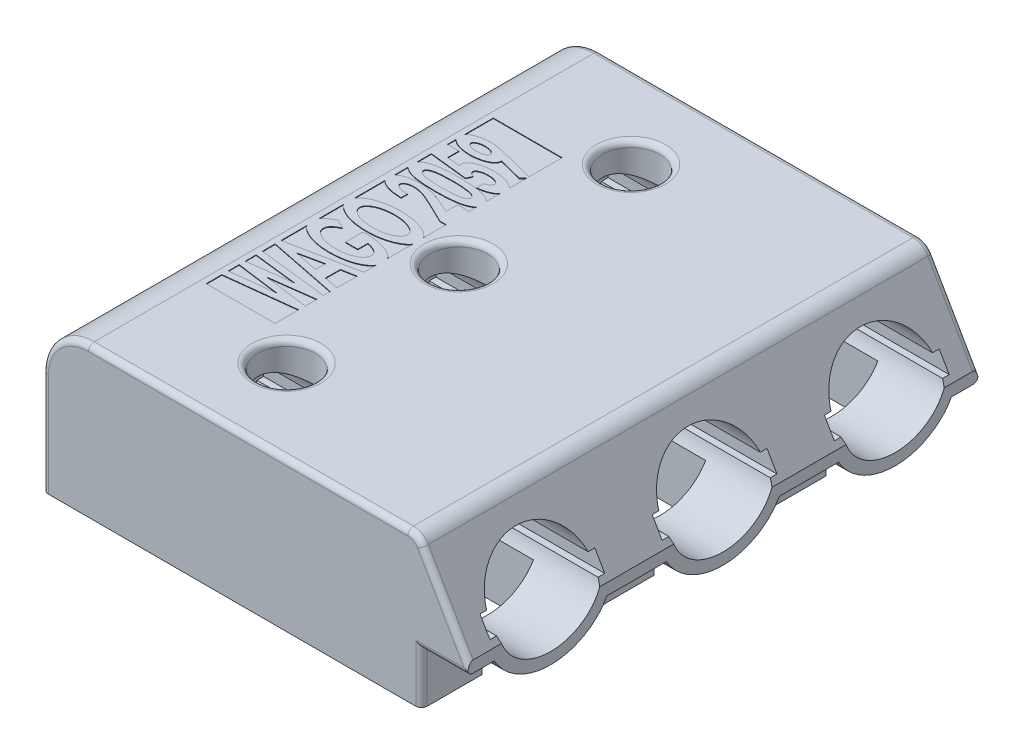
SolidWorks part; units mm, degrees
material "ABS"
ref_plane "Front Plane" through (0, 0, 0) normal (0, 0, 1) x (1, 0, 0)
ref_plane "Top Plane" through (0, 0, 0) normal (0, 1, 0) x (1, 0, 0)
ref_plane "Right Plane" through (0, 0, 0) normal (1, 0, 0) x (0, 0, -1)
sketch "Sketch1" plane through (0, 0, 0) normal (0, 1, 0) x (1, 0, 0)
  line L1 (0, 0) -> (7.4, 0)
  line L2 (0, 0) -> (0, 8.9)
  line L3 (0, 8.9) -> (7.4, 8.9)
  line L4 (7.4, 0) -> (7.4, 8.9)
  dimension "D1" = 8.9
  dimension "D2" = 7.4
extrude "Boss-Extrude1" add sketch "Sketch1" along normal blind 2.6
sketch "Sketch2" plane through (7.4, 0, 0) normal (1, 0, 0) x (0, 0, -1)
  line L0 (0, 2.6) -> (0, 0) construction
  line L1 (0, 0) -> (8.9, 0) construction
  ellipse E0 centre (1.45, 1.35) end of major axis (2.35, 1.35) minor radius 0.8
  ellipse E1 centre (4.45, 1.35) end of major axis (5.35, 1.35) minor radius 0.8
  ellipse E2 centre (7.45, 1.35) end of major axis (8.35, 1.35) minor radius 0.8
  dimension "D1" = 1.45
  dimension "D2" = 1.35
extrude "Cut-Extrude1" cut sketch "Sketch2" against normal blind 6
sketch "Sketch3" plane through (0, 2.6, 0) normal (0, 1, 0) x (1, 0, 0)
  line L0 (0, 8.9) -> (0, 0) construction
  line L1 (0, 0) -> (7.4, 0) construction
  circle A0 centre (2.8, 1.45) radius 0.5
  circle A1 centre (2.8, 4.45) radius 0.5
  circle A2 centre (2.8, 7.45) radius 0.5
  dimension "D1" = 1
  dimension "D3" = 1.45
  dimension "D2" = 2.8
  dimension "D4" = 3
extrude "Cut-Extrude2" cut sketch "Sketch3" against normal up to next
sketch "Sketch4" plane through (7.4, 0, 0) normal (1, 0, 0) x (0, 0, -1)
  line L0 (0, 2.6) -> (0, 0) construction
  line L1 (0.45, 1.5) -> (2.45, 1.5)
  line L2 (0.45, 1.5) -> (0.45, 1.2)
  line L3 (0.45, 1.2) -> (2.45, 1.2)
  line L4 (2.45, 1.5) -> (2.45, 1.2)
  line L6 (0, 0) -> (8.9, 0) construction
  line L7 (8.9, 2.6) -> (8.9, 0) construction
  line L8 (3.45, 1.5) -> (5.45, 1.5)
  line L9 (3.45, 1.5) -> (3.45, 1.2)
  line L10 (3.45, 1.2) -> (5.45, 1.2)
  line L11 (5.45, 1.5) -> (5.45, 1.2)
  line L12 (6.45, 1.5) -> (8.45, 1.5)
  line L13 (6.45, 1.5) -> (6.45, 1.2)
  line L14 (6.45, 1.2) -> (8.45, 1.2)
  line L15 (8.45, 1.5) -> (8.45, 1.2)
  dimension "D1" = 0.3
  dimension "D2" = 2
  dimension "D3" = 0.45
  dimension "D4" = 1.2
  dimension "D5" = 2
  dimension "D6" = 2
  dimension "D7" = 0.3
  dimension "D8" = 0.3
  dimension "D9" = 1.2
  dimension "D10" = 1.2
  dimension "D11" = 0.45
  dimension "D12" = 1
extrude "Cut-Extrude3" cut sketch "Sketch4" against normal blind 6
chamfer "Chamfer2" distance 1.5 angle 30 1 edges at (7.4, 2.6, -4.45) first distance on face at (7.4, 1.35, -7.45)
sketch "Sketch5" plane through (0, 0, 0) normal (0, -1, 0) x (1, 0, 0)
  line L1 (0.8, -8.25) -> (6.3, -8.25)
  line L2 (0.8, -8.25) -> (0.8, -6.65)
  line L3 (0.8, -6.65) -> (6.3, -6.65)
  line L4 (6.3, -8.25) -> (6.3, -6.65)
  line L5 (0, -8.9) -> (0, 0) construction
  line L6 (7.4, -8.9) -> (0, -8.9) construction
  line L7 (0.8, -5.25) -> (6.3, -5.25)
  line L8 (0.8, -5.25) -> (0.8, -3.65)
  line L9 (0.8, -3.65) -> (6.3, -3.65)
  line L10 (6.3, -5.25) -> (6.3, -3.65)
  line L11 (0.8, -2.25) -> (6.3, -2.25)
  line L12 (0.8, -2.25) -> (0.8, -0.65)
  line L13 (0.8, -0.65) -> (6.3, -0.65)
  line L14 (6.3, -2.25) -> (6.3, -0.65)
  dimension "D1" = 1.6
  dimension "D2" = 0.65
  dimension "D3" = 0.8
  dimension "D4" = 5.5
  dimension "D5" = 3
extrude "Cut-Extrude4" cut sketch "Sketch5" against normal blind 0.4
sketch "Sketch6" plane through (0, 0, 0) normal (0, -1, 0) x (1, 0, 0)
  line L0 (0, -8.9) -> (0, 0) construction
  line L1 (0, -7.85) -> (0.8, -7.85)
  line L2 (0, -7.85) -> (0, -7.05)
  line L3 (0, -7.05) -> (0.8, -7.05)
  line L4 (0.8, -7.85) -> (0.8, -7.05)
  line L5 (0.8, -6.65) -> (0.8, -8.25) construction
  line L6 (0.8, -8.25) -> (6.3, -8.25) construction
  line L7 (0, -4.85) -> (0.8, -4.85)
  line L8 (0, -4.85) -> (0, -4.05)
  line L9 (0, -4.05) -> (0.8, -4.05)
  line L10 (0.8, -4.85) -> (0.8, -4.05)
  line L11 (0, -1.85) -> (0.8, -1.85)
  line L12 (0, -1.85) -> (0, -1.05)
  line L13 (0, -1.05) -> (0.8, -1.05)
  line L14 (0.8, -1.85) -> (0.8, -1.05)
  line L15 (6.3, -8.25) -> (6.3, -6.65) construction
  line L16 (6.3, -7.85) -> (7.4, -7.85)
  line L17 (6.3, -7.85) -> (6.3, -7.05)
  line L18 (6.3, -7.05) -> (7.4, -7.05)
  line L19 (7.4, -7.85) -> (7.4, -7.05)
  line L20 (7.4, 0) -> (7.4, -8.9) construction
  line L21 (6.3, -4.85) -> (7.4, -4.85)
  line L22 (6.3, -4.85) -> (6.3, -4.05)
  line L23 (6.3, -4.05) -> (7.4, -4.05)
  line L24 (7.4, -4.85) -> (7.4, -4.05)
  line L25 (6.3, -1.85) -> (7.4, -1.85)
  line L26 (6.3, -1.85) -> (6.3, -1.05)
  line L27 (6.3, -1.05) -> (7.4, -1.05)
  line L28 (7.4, -1.85) -> (7.4, -1.05)
  dimension "D1" = 0.8
  dimension "D2" = 0.4
  dimension "D4" = 0.8
  dimension "D5" = 0.4
  dimension "D3" = 3
extrude "Cut-Extrude5" cut sketch "Sketch6" against normal blind 0.2
sketch "Sketch7" plane through (0, 0.4, 0) normal (0, -1, 0) x (1, 0, 0)
  line L0 (6.3, -6.65) -> (0.8, -6.65) construction
  line L1 (6.3, -8.25) -> (2.7, -8.25)
  line L2 (6.3, -8.25) -> (6.3, -6.65)
  line L3 (6.3, -6.65) -> (2.7, -6.65)
  line L4 (2.7, -8.25) -> (2.7, -6.65)
  line L5 (6.3, -5.25) -> (2.7, -5.25)
  line L6 (6.3, -5.25) -> (6.3, -3.65)
  line L7 (6.3, -3.65) -> (2.7, -3.65)
  line L8 (2.7, -5.25) -> (2.7, -3.65)
  line L9 (6.3, -2.25) -> (2.7, -2.25)
  line L10 (6.3, -2.25) -> (6.3, -0.65)
  line L11 (6.3, -0.65) -> (2.7, -0.65)
  line L12 (2.7, -2.25) -> (2.7, -0.65)
  dimension "D1" = 3.6
extrude "Cut-Extrude6" cut sketch "Sketch7" against normal up to next
fillet "Fillet1" radius 0.8 1 edges at (0, 2.6, -4.45)
fillet "Fillet2" radius 0.1 3 edges at (2.8, 2.6, -0.95) (2.8, 2.6, -3.95) (2.8, 2.6, -6.95)
sketch "Sketch8" plane through (7.4, 0, 0) normal (1, 0, 0) x (0, 0, -1)
  line L0 (0, 0) -> (0, 0.9)
  line L1 (0, 1.1) -> (0, 0) construction
  line L3 (0, 0.9) -> (0.4677, 0.9)
  line L4 (8.9, 1.1) -> (8.9, 0) construction
  line L5 (8.9, 0.9) -> (8.9, 0)
  line L6 (8.9, 0) -> (0, 0)
  line L7 (2.4323, 0.9) -> (3.4677, 0.9)
  line L8 (5.4323, 0.9) -> (6.4677, 0.9)
  line L9 (8.4323, 0.9) -> (8.9, 0.9)
  ellipse E0 centre (1.45, 1.35) end of major axis (2.55, 1.35) minor radius 1 (0.4677, 0.9) -> (2.4323, 0.9) ccw
  ellipse E2 centre (1.45, 1.35) end of major axis (2.35, 1.35) minor radius 0.8 (2.334, 1.5) -> (0.566, 1.5) ccw construction
  ellipse E3 centre (4.45, 1.35) end of major axis (3.35, 1.35) minor radius 1 (3.4677, 0.9) -> (5.4323, 0.9) ccw
  ellipse E4 centre (7.45, 1.35) end of major axis (6.35, 1.35) minor radius 1 (6.4677, 0.9) -> (8.4323, 0.9) ccw
  dimension "D1" = 0.9
extrude "Cut-Extrude7" cut sketch "Sketch8" against normal blind 0.8
fillet "Fillet3" radius 0.1 12 edges at (0, 0.9, -8.9) (0.2343, 2.3657, -8.9) (0, 0.9, 0) (0.2343, 2.3657, 0) (6.6, 0.45, -8.9) (7, 0.9, -8.9) (3.667, 2.6, -8.9) (6.967, 1.85, -8.9) (6.6, 0.45, 0) (7, 0.9, 0) (3.667, 2.6, 0) (6.967, 1.85, 0)
fillet "Fillet4" radius 0.3 3 edges at (6.5171, 2.5707, -8.8707) (6.5171, 2.5707, -0.0293) (6.534, 2.6, -4.45)
sketch "Sketch10" plane through (0, 2.6, 0) normal (0, 1, 0) x (1, 0, 0)
  line L0 (6.3608, 0) -> (0.8, 0) construction
  line L1 (0.9, 1.95) -> (2.1, 1.95)
  line L2 (0.9, 1.95) -> (0.9, 6.95)
  line L3 (0.9, 6.95) -> (2.1, 6.95)
  line L4 (2.1, 1.95) -> (2.1, 6.95)
  line L5 (0, 0.1) -> (0, 8.8) construction
  dimension "D1" = 1.2
  dimension "D2" = 5
  dimension "D3" = 1.95
  dimension "D4" = 0.9
extrude "Cut-Extrude8" cut sketch "Sketch10" against normal blind 0.01
sketch "Sketch13" plane through (0, 2.59, 0) normal (0, 1, 0) x (1, 0, 0)
  text T0 "<b>WAGO 2059</b>" font "Century Gothic" height 1.2
extrude "Boss-Extrude2" add sketch "Sketch13" along normal blind 0.01
